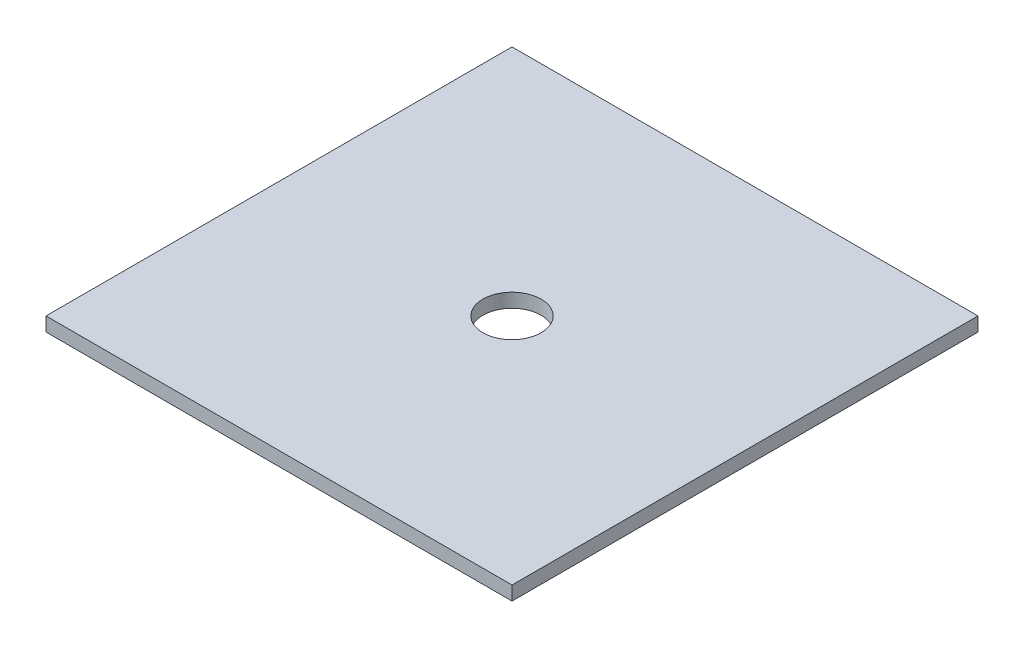
SolidWorks part; units mm, degrees
ref_plane "Front Plane" through (0, 0, 0) normal (0, 0, 1) x (1, 0, 0)
ref_plane "Top Plane" through (0, 0, 0) normal (0, 1, 0) x (1, 0, 0)
ref_plane "Right Plane" through (0, 0, 0) normal (1, 0, 0) x (0, 0, -1)
sketch "Sketch1" plane through (0, 0, 0) normal (0, 1, 0) x (1, 0, 0)
  line L1 (-100, -100) -> (100, -100)
  line L2 (-100, -100) -> (-100, 100)
  line L3 (-100, 100) -> (100, 100)
  line L4 (100, -100) -> (100, 100)
  line L5 (0, 100) -> (0, -100) construction
  line L6 (-100, 0) -> (100, 0) construction
  point P0 (0, 0)
  dimension "D1" = 200
  dimension "D2" = 200
extrude "Boss-Extrude1" add sketch "Sketch1" along normal blind 6
sketch "Sketch2" plane through (0, 6, 0) normal (0, 1, 0) x (1, 0, 0)
  circle A0 centre (0, 0) radius 12.5
  dimension "D1" = 25
extrude "Cut-Extrude1" cut sketch "Sketch2" against normal blind 24
